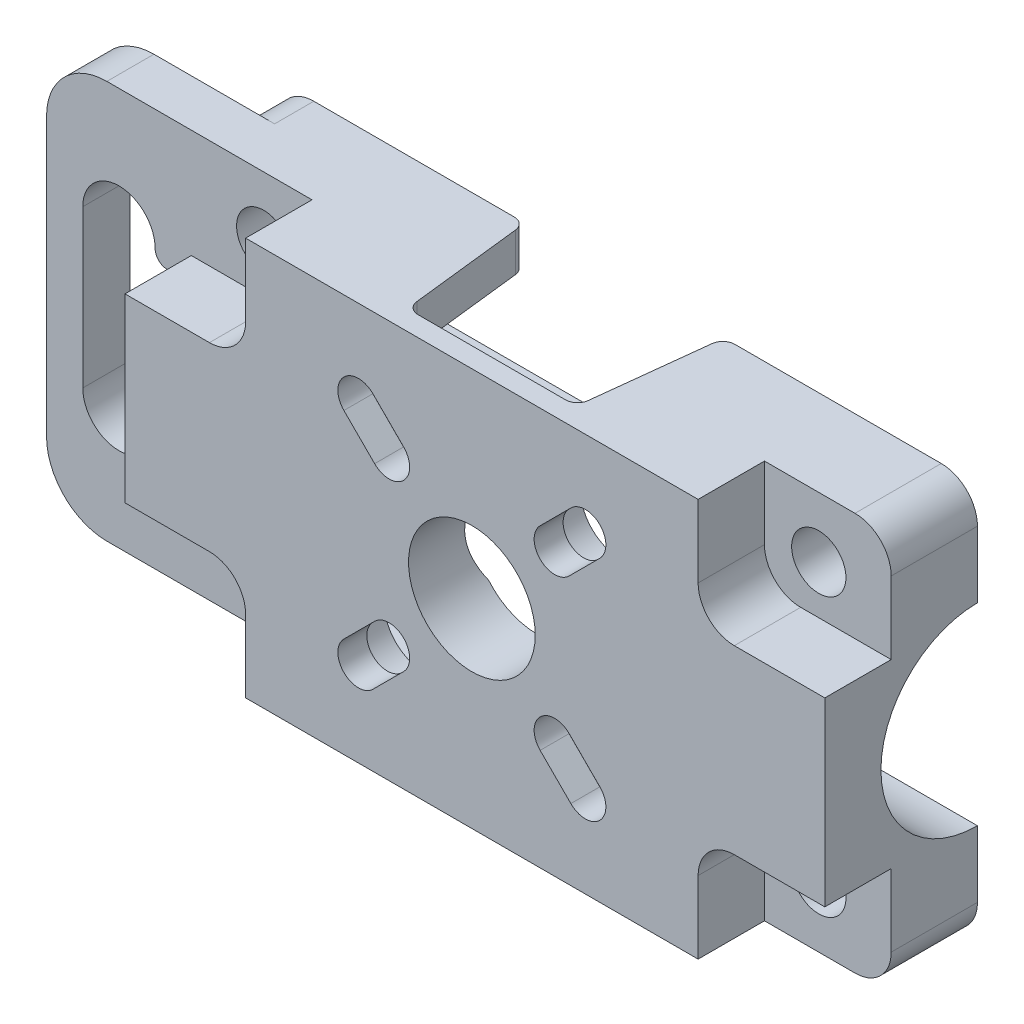
SolidWorks part; units mm, degrees
material "ABS"
ref_plane "Front Plane" through (0, 0, 0) normal (0, 0, 1) x (1, 0, 0)
ref_plane "Top Plane" through (0, 0, 0) normal (0, 1, 0) x (1, 0, 0)
ref_plane "Right Plane" through (0, 0, 0) normal (1, 0, 0) x (0, 0, -1)
sketch "Sketch2" plane through (0, 0, 0) normal (0, 0, 1) x (1, 0, 0)
  line L1 (32, 16.5) -> (-30, 16.5)
  line L2 (35, 13.5) -> (35, -13.5)
  line L3 (32, -16.5) -> (-30, -16.5)
  line L4 (-35, 11.5) -> (-35, -11.5)
  line L5 (35, 16.5) -> (-35, -16.5) construction
  line L6 (35, -16.5) -> (-35, 16.5) construction
  arc A0 (35, -13.5) -> (32, -16.5) centre (32, -13.5) cw
  arc A1 (32, 16.5) -> (35, 13.5) centre (32, 13.5) cw
  arc A2 (-30, -16.5) -> (-35, -11.5) centre (-30, -11.5) cw
  arc A3 (-30, 16.5) -> (-35, 11.5) centre (-30, 11.5) ccw
  point P0 (0, 0)
  dimension "D3" = 3
  dimension "D4" = 5
  dimension "D1" = 33
  dimension "D2" = 70
extrude "Boss-Extrude1" add sketch "Sketch2" along normal blind 12.65
sketch "Sketch3" plane through (0, 0, 12.65) normal (0, 0, 1) x (1, 0, 0)
  line L0 (24.5, 16.5) -> (24.5, 10.5)
  line L1 (32, 16.5) -> (-30, 16.5) construction
  line L2 (27.5, 7.5) -> (35, 7.5)
  line L3 (35, -13.5) -> (35, 13.5) construction
  line L4 (-30, -16.5) -> (32, -16.5) construction
  line L5 (-30, -16.5) -> (-13, -16.5)
  line L6 (32, 16.5) -> (24.5, 16.5)
  line L7 (35, -13.5) -> (35, 13.5)
  line L8 (24.5, -10.5) -> (24.5, -16.5)
  line L9 (27.5, -7.5) -> (35, -7.5)
  line L10 (-35, 11.5) -> (-35, -11.5) construction
  line L11 (-35, 11.5) -> (-35, -11.5)
  line L12 (-13, 16.5) -> (-13, 10.5)
  line L13 (-16, 7.5) -> (-23, 7.5)
  line L14 (-23, 7.5) -> (-23, -7.5)
  line L15 (-23, -7.5) -> (-16, -7.5)
  line L16 (-13, -10.5) -> (-13, -16.5)
  line L17 (-13, 16.5) -> (-30, 16.5)
  line L18 (24.5, -16.5) -> (32, -16.5)
  arc A0 (32, -16.5) -> (35, -13.5) centre (32, -13.5) ccw construction
  arc A1 (35, 13.5) -> (32, 16.5) centre (32, 13.5) ccw construction
  arc A2 (32, -16.5) -> (35, -13.5) centre (32, -13.5) ccw
  arc A3 (35, 13.5) -> (32, 16.5) centre (32, 13.5) ccw
  arc A4 (-35, -11.5) -> (-30, -16.5) centre (-30, -11.5) ccw construction
  arc A5 (-30, 16.5) -> (-35, 11.5) centre (-30, 11.5) ccw construction
  arc A6 (-35, -11.5) -> (-30, -16.5) centre (-30, -11.5) ccw
  arc A7 (-30, 16.5) -> (-35, 11.5) centre (-30, 11.5) ccw
  arc A8 (24.5, 10.5) -> (27.5, 7.5) centre (27.5, 10.5) ccw
  arc A9 (24.5, -10.5) -> (27.5, -7.5) centre (27.5, -10.5) cw
  arc A10 (-16, -7.5) -> (-13, -10.5) centre (-16, -10.5) cw
  arc A11 (-13, 10.5) -> (-16, 7.5) centre (-16, 10.5) cw
  point P28 (24.5, 7.5)
  point P31 (24.5, -7.5)
  point P34 (-13, -7.5)
  point P37 (-13, 7.5)
  arc M7 (32, -16.5) -> (35, -13.5) centre (32, -13.5) ccw
  line M8 (35, -13.5) -> (35, 13.5)
  arc M9 (35, 13.5) -> (32, 16.5) centre (32, 13.5) ccw
  line M10 (32, 16.5) -> (-30, 16.5)
  arc M11 (-30, 16.5) -> (-35, 11.5) centre (-30, 11.5) ccw
  line M12 (-35, 11.5) -> (-35, -11.5)
  arc M13 (-35, -11.5) -> (-30, -16.5) centre (-30, -11.5) ccw
  line M14 (-30, -16.5) -> (32, -16.5)
  dimension "D6" = 3
  dimension "D1" = 10.5
  dimension "D2" = 9
  dimension "D3" = 22
  dimension "D4" = 12
  dimension "D5" = 9
extrude "Cut-Extrude1" cut sketch "Sketch3" against normal blind 5.5 contours A11 L12 L16 A10 L15 L14 L13 M10 M11 M12 M13 M14 | L0 A8 L2 M8 M9 M10 | A9 L8 L9 M14 M7 M8 region at (29.75, 12, 12.65) region at (-25.4853, 0, 12.65) region at (29.75, -12, 12.65)
sketch "Sketch4" plane through (35, 0, 0) normal (1, 0, 0) x (0, 0, -1)
  line L0 (0, -13.5) -> (0, 13.5) construction
  line L1 (0, -8) -> (0, 8)
  arc A0 (0, -8) -> (0, 8) centre (0, 0) cw
  dimension "D1" = 8
sketch "Sketch5" plane through (0, 0, 7.15) normal (0, 0, 1) x (1, 0, 0)
  line L0 (-23, -5.5) -> (-24.9958, -5.5)
  line L1 (-23, 7.5) -> (-23, -7.5) construction
  line L2 (-23, 5.5) -> (-24.9958, 5.5)
  line L3 (-23, 5.5) -> (-23, -5.5)
  line L4 (-31.9994, -6.5037) -> (-31.9994, 6.5037)
  line L5 (-35, 11.5) -> (-35, -11.5) construction
  line L6 (0, 0) -> (-50000, 0) construction
  arc A2 (-25.9994, 6.5037) -> (-31.9994, 6.5037) centre (-28.9994, 6.5037) ccw
  arc A3 (-25.9994, -6.5037) -> (-31.9994, -6.5037) centre (-28.9994, -6.5037) cw
  arc A4 (-25.9994, 6.5037) -> (-24.9958, 5.5) centre (-24.9958, 6.5037) ccw
  arc A5 (-25.9994, -6.5037) -> (-24.9958, -5.5) centre (-24.9958, -6.5037) cw
  point P10 (-31.9994, 0)
  point P15 (-23, 0)
  dimension "D1" = 1.0037
  dimension "D2" = 3
  dimension "D3" = 11
  dimension "D4" = 3.0006
extrude "Cut-Extrude3" cut sketch "Sketch5" against normal through all
extrude "Cut-Extrude4" cut sketch "Sketch4" against normal up to surface (58 mm away) up to face at (-23, 0, 6.7375)
sketch "Sketch6" plane through (0, 0, 0) normal (0, 0, -1) x (-1, 0, 0)
  line L0 (30, -16.5) -> (-32, -16.5) construction
  line L1 (-32, 16.5) -> (30, 16.5) construction
  line L2 (35, 11.5) -> (35, -11.5) construction
  line L3 (30, -16.5) -> (20, -16.5)
  line L4 (20, 16.5) -> (30, 16.5)
  line L5 (35, 11.5) -> (35, -11.5)
  line L6 (23, -13.5) -> (23, 13.5)
  arc A0 (35, 11.5) -> (30, 16.5) centre (30, 11.5) ccw construction
  arc A1 (30, -16.5) -> (35, -11.5) centre (30, -11.5) ccw construction
  arc A2 (35, 11.5) -> (30, 16.5) centre (30, 11.5) ccw
  arc A3 (30, -16.5) -> (35, -11.5) centre (30, -11.5) ccw
  arc A4 (23, 13.5) -> (20, 16.5) centre (20, 13.5) ccw
  arc A5 (23, -13.5) -> (20, -16.5) centre (20, -13.5) cw
  dimension "D1" = 3
  dimension "D2" = 15
extrude "Cut-Extrude5" cut sketch "Sketch6" against normal blind 3.25
sketch "Sketch7" plane through (0, 0, 0) normal (0, 0, -1) x (-1, 0, 0)
  line L0 (-32, 13.5) -> (20, -13.5) construction
  line L1 (9.5, -13.3) -> (-21.5, -13.3)
  line L2 (11.5, -11.3) -> (11.5, 11.3)
  line L3 (9.5, 13.3) -> (-21.5, 13.3)
  line L4 (-23.5, -11.3) -> (-23.5, 11.3)
  line L5 (11.5, -13.3) -> (-23.5, 13.3) construction
  line L6 (11.5, 13.3) -> (-23.5, -13.3) construction
  arc A0 (11.5, 11.3) -> (9.5, 13.3) centre (9.5, 11.3) ccw
  arc A1 (9.5, -13.3) -> (11.5, -11.3) centre (9.5, -11.3) ccw
  arc A2 (-21.5, -13.3) -> (-23.5, -11.3) centre (-21.5, -11.3) cw
  arc A3 (-21.5, 13.3) -> (-23.5, 11.3) centre (-21.5, 11.3) ccw
  point P0 (-6, 0)
  point P9 (-6, 0)
  dimension "D3" = 2
  dimension "D1" = 35
  dimension "D2" = 26.6
extrude "Cut-Extrude6" cut sketch "Sketch7" against normal blind 7.25
hole_wizard "M10 Clearance Hole1" positions "Sketch8" profile "Sketch9" hole size "M10" standard "ANSI Metric" end condition through all
sketch "Sketch8" plane through (0, 0, 12.65) normal (0, 0, 1) x (1, 0, 0)
  line L0 (24.5, -16.5) -> (-13, 16.5) construction
  point P0 (5.75, 0)
sketch "Sketch9" plane through (5.75, 0, 12.65) normal (1, 0, 0) x (0, -1, 0)
  line L0 (0, 0) -> (0, 12.65)
  line L1 (0, 12.65) -> (5.25, 12.65)
  line L2 (5.25, 12.65) -> (5.25, 0)
  line L5 (5.25, 0) -> (0, 0)
  line L11 (0, -6.35) -> (0, 107.95) construction
  dimension "Thru Hole Dia." = 10.5
  dimension "Thru Hole Depth" = 12.65
hole_wizard "CBORE SLOT for M3 SHCS1" positions "Sketch14" profile "Sketch11" size "M3" standard "ANSI Metric" slot yes end condition up to next
sketch "Sketch14" plane through (0, 0, 7.25) normal (0, 0, -1) x (-1, 0, 0)
  line L0 (-11.4069, -5.6569) -> (-16.3566, -10.6066) construction
  line L1 (-5.75, 0) -> (-11.4069, -5.6569) construction
  line L3 (-5.75, 0) -> (-5.75, -5.6569) construction
  line L4 (-5.75, -5.6569) -> (-11.4069, -5.6569) construction
  point P0 (-13.8817, -8.1317)
  dimension "D1" = 7
  dimension "D2" = 8
sketch "Sketch11" plane through (13.8817, -8.1317, 7.25) normal (1, 0, 0) x (0, 1, 0)
  line L0 (0, 0) -> (0, 5.4)
  line L1 (0, 5.4) -> (1.7, 5.4)
  line L3 (1.7, 5.4) -> (1.7, 3)
  line L4 (1.7, 3) -> (3.25, 3)
  line L5 (3.25, 3) -> (3.25, 0)
  line L7 (3.25, 0) -> (0, 0)
  line L11 (0, -6.35) -> (0, 107.95) construction
  dimension "Thru Hole Dia." = 3.4
  dimension "Thru Hole Depth" = 5.4
  dimension "C'Bore Dia." = 6.5
  dimension "C'Bore Depth" = 3
pattern_circular "CirPattern1" count 4 over 360 about axis through (5.75, 0, 12.65) along (0, 0, 1) of "CBORE SLOT for M3 SHCS1"
hole_wizard "M4 Clearance Hole1" positions "Sketch17" profile "Sketch18" hole size "M4" standard "ANSI Metric" end condition up to next
sketch "Sketch17" plane through (0, 0, 7.15) normal (0, 0, 1) x (1, 0, 0)
  line L0 (29, 11.5) -> (29, -11.5) construction
  line L3 (0, 0) -> (50000, 0) construction
  line L4 (-17, 11.5) -> (-17, -11.5) construction
  line L6 (35, 7.5) -> (35, 13.5) construction
  point P0 (29, -11.5)
  point P2 (29, 11.5)
  point P5 (-17, 11.5)
  point P7 (-17, -11.5)
  point P18 (29, 0)
  point P25 (-17, 0)
  dimension "D1" = 23
  dimension "D2" = 6
  dimension "D3" = 46
sketch "Sketch18" plane through (29, -11.5, 7.15) normal (1, 0, 0) x (0, -1, 0)
  line L0 (0, 0) -> (0, 7.15)
  line L1 (0, 7.15) -> (2.25, 7.15)
  line L2 (2.25, 7.15) -> (2.25, 0)
  line L5 (2.25, 0) -> (0, 0)
  line L11 (0, -6.35) -> (0, 107.95) construction
  dimension "Thru Hole Dia." = 4.5
  dimension "Thru Hole Depth" = 7.15
sketch "Sketch19" plane through (-23, 0, 0) normal (1, 0, 0) x (0, 0, -1)
  line L2 (-3.25, 5.5) -> (-3.25, 7.3101)
  line L3 (-5.8095, 5.5) -> (-3.25, 5.5)
  line L4 (-3.25, 5.5) -> (-3.25, 7.3101)
  line L5 (-5.8095, 5.5) -> (-3.25, 5.5)
  line L6 (-3.25, -7.3101) -> (-3.25, -5.5)
  line L7 (-3.25, -5.5) -> (-5.8095, -5.5)
  line L8 (-3.25, -7.3101) -> (-3.25, -5.5)
  line L9 (-3.25, -5.5) -> (-5.8095, -5.5)
  arc A1 (-3.25, 7.3101) -> (-5.8095, 5.5) centre (0, 0) ccw
  arc A2 (-3.25, 7.3101) -> (-5.8095, 5.5) centre (0, 0) ccw
  arc A3 (-5.8095, -5.5) -> (-3.25, -7.3101) centre (0, 0) ccw
  arc A4 (-5.8095, -5.5) -> (-3.25, -7.3101) centre (0, 0) ccw
  dimension "D1" = 0
  dimension "D2" = 0
extrude "Boss-Extrude2" add sketch "Sketch19" along normal blind 4
sketch "Sketch20" plane through (0, 16.5, 0) normal (0, 1, 0) x (1, 0, 0)
  line L0 (-2.5, 0) -> (14, 0)
  line L1 (32, 0) -> (-20, 0) construction
  line L2 (12.75, -11) -> (-1.25, -11)
  line L3 (5.75, 0) -> (5.75, -12.65) construction
  line L4 (24.5, -12.65) -> (-13, -12.65) construction
  line L5 (14, 0) -> (12.75, -11)
  line L6 (-1.25, -11) -> (-2.5, 0)
  point P11 (5.75, -11)
  dimension "D1" = 16.5
  dimension "D2" = 14
  dimension "D3" = 11
extrude "Cut-Extrude7" cut sketch "Sketch20" against normal blind 3.2
fillet "Fillet1" radius 1 4 edges at (14, 14.9, 0) (-2.5, 14.9, 0) (-1.25, 14.9, 11) (12.75, 14.9, 11)
mirror "Mirror1" about plane through (0, 0, 0) normal (0, 1, 0) of "Fillet1", "Cut-Extrude7"
